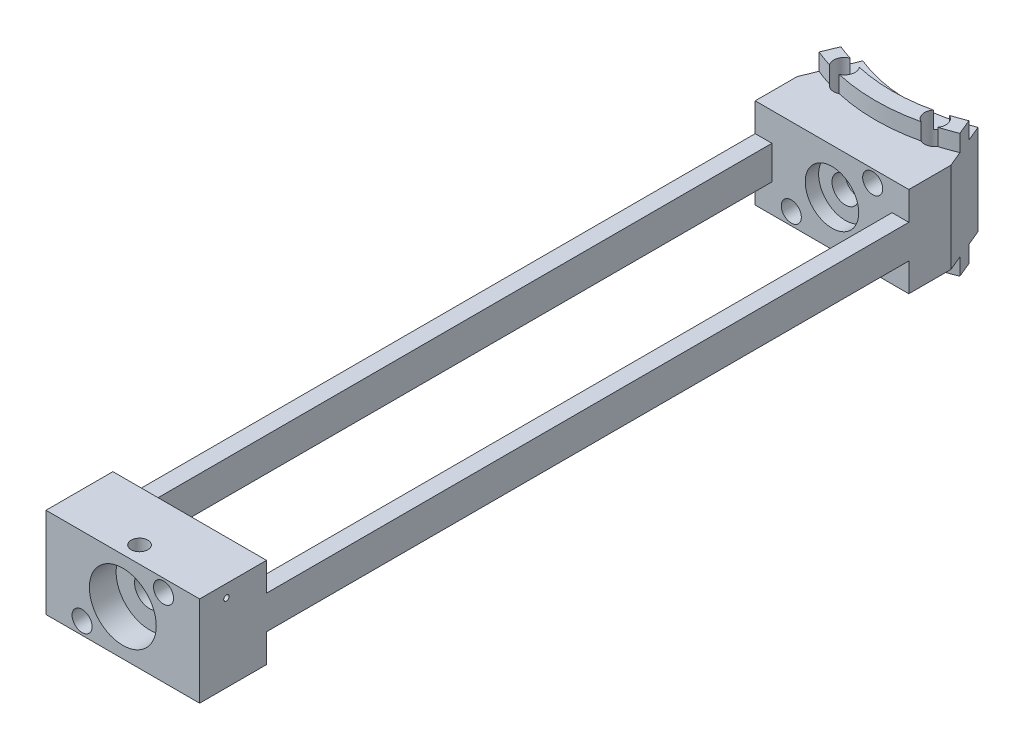
SolidWorks part; units mm, degrees
note: The reader was unsure of these and kept them because the rebuilt part matched: shared geometry of "Sketch1<3>".
ref_plane "Front Plane" through (0, 0, 0) normal (0, 0, 1) x (1, 0, 0)
ref_plane "Top Plane" through (0, 0, 0) normal (0, 1, 0) x (1, 0, 0)
ref_plane "Right Plane" through (0, 0, 0) normal (1, 0, 0) x (0, 0, -1)
sketch "Sketch1" plane through (0, 0, 0) normal (0, 1, 0) x (1, 0, 0)
  line L0 (0, 0) -> (-22.961, -55.4328)
  line L1 (0, 0) -> (22.961, -55.4328)
  line L2 (0, 0) -> (0, -29.5283) construction
  circle A0 centre (0, 0) radius 60
  circle A1 centre (0, 0) radius 55
  circle A2 centre (0, 0) radius 50
  circle A3 centre (0, 0) radius 45
  dimension "D1" = 120
  dimension "D2" = 5
  dimension "D3" = 5
  dimension "D4" = 5
  dimension "D5" = 45
extrude "Boss-Extrude1" add sketch "Sketch1" along normal mid plane 27 contours A1 L0 A0 L1 | A2 L0 A1 L1 | A3 L0 A2 L1
extrude "Boss-Extrude2" add sketch "Sketch1<3>" along normal mid plane 37 contours A2 L0 A1 L1
sketch "Sketch1<3>" plane through (0, 0, 0) normal (0, 1, 0) x (1, 0, 0) same geometry as "Sketch1"
ref_plane "Plane1" through (0, 0, 60) normal (0, 0, 1) x (1, 0, 0)
sketch "Sketch3" plane through (0, 0, 0) normal (0, -1, 0) x (1, 0, 0)
  line L0 (-22.961, 55.4328) -> (-22.961, 280)
  line L1 (-22.961, 280) -> (22.961, 280)
  line L2 (22.961, 280) -> (22.961, 55.4328)
  line L3 (-17.961, 57.2486) -> (-17.961, 260)
  line L4 (-17.961, 260) -> (17.961, 260)
  line L5 (17.961, 260) -> (17.961, 57.2486)
  arc A0 (22.961, 55.4328) -> (-22.961, 55.4328) centre (0, 0) ccw construction
  arc A1 (22.961, 55.4328) -> (-22.961, 55.4328) centre (0, 0) ccw
  dimension "D1" = 5
  dimension "D2" = 5
  dimension "D3" = 20
  dimension "D4" = 280
extrude "Boss-Extrude3" add sketch "Sketch3" against normal mid plane 10 contours L3 A1 L0 L1 L2 L5 L4
sketch "Sketch4" plane through (0, 0, 0) normal (0, 1, 0) x (1, 0, 0)
  line L0 (22.961, -280) -> (22.961, -55.4328) construction
  line L1 (-22.961, -280) -> (22.961, -280)
  line L2 (-22.961, -280) -> (-22.961, -260)
  line L3 (-22.961, -260) -> (22.961, -260)
  line L4 (22.961, -280) -> (22.961, -260)
  line L5 (-17.961, -260) -> (17.961, -260) construction
extrude "Boss-Extrude4" add sketch "Sketch4" along normal mid plane 27
sketch "Sketch2" plane through (0, 0, 0) normal (0, 0, 1) x (1, 0, 0)
  circle A0 centre (0, 0) radius 4
  dimension "D1" = 8
extrude "Cut-Extrude1" cut sketch "Sketch2" along normal through all
sketch "Sketch5" plane through (0, 0, 260) normal (0, 0, -1) x (-1, 0, 0)
  circle A0 centre (0, 0) radius 8
  dimension "D1" = 16
extrude "Cut-Extrude2" cut sketch "Sketch5" against normal blind 4 contours A0
sketch "Sketch6" plane through (0, 0, 280) normal (0, 0, 1) x (1, 0, 0)
  circle A0 centre (0, 0) radius 10
  dimension "D1" = 20
extrude "Cut-Extrude3" cut sketch "Sketch6" against normal blind 8
sketch "Sketch7" plane through (0, 0, 280) normal (0, 0, 1) x (1, 0, 0)
  circle A0 centre (0, 0) radius 10
  dimension "D1" = 20
sketch "Sketch9" plane through (0, 0, 0) normal (0, 1, 0) x (1, 0, 0)
  line L0 (-22.961, -55.4328) -> (-22.961, -68)
  line L1 (-22.961, -55.4328) -> (-22.961, -260) construction
  line L2 (-22.961, -68) -> (22.961, -68)
  line L3 (22.961, -260) -> (22.961, -55.4328) construction
  line L4 (22.961, -68) -> (22.961, -55.4328)
  arc A0 (-22.961, -55.4328) -> (22.961, -55.4328) centre (0, 0) ccw construction
  arc A1 (-22.961, -55.4328) -> (22.961, -55.4328) centre (0, 0) ccw
  point P3 (0, -60)
  dimension "D1" = 8
extrude "Boss-Extrude5" add sketch "Sketch9" along normal mid plane 27
sketch "Sketch8" plane through (0, 0, 60) normal (0, 0, 1) x (1, 0, 0)
  circle A0 centre (0, 0) radius 9
  dimension "D1" = 18
extrude "Cut-Extrude5" cut sketch "Sketch8" against normal up to next
sketch "Sketch10" plane through (0, 0, 60) normal (0, 0, 1) x (1, 0, 0)
  circle A0 centre (0, 0) radius 4
  dimension "D1" = 8
extrude "Cut-Extrude6" cut sketch "Sketch10" along normal up to next
sketch "Sketch11" plane through (0, 0, 68) normal (0, 0, 1) x (1, 0, 0)
  circle A0 centre (0, 0) radius 8
  dimension "D1" = 16
extrude "Cut-Extrude7" cut sketch "Sketch11" against normal blind 4
sketch "Sketch15" plane through (0, 0, 280) normal (0, 0, 1) x (1, 0, 0)
  circle A0 centre (-12.1674, -9.7628) radius 3
  circle A1 centre (12.1674, 9.7628) radius 3
  dimension "D1" = 6
extrude "Cut-Extrude8" cut sketch "Sketch15" against normal up to vertex (224.5672 mm away) contours A0 | A1
hole_wizard "M2 Tapped Hole1" positions "Sketch16" profile "Sketch17" tap size "M2" standard "ISO"
sketch "Sketch16" plane through (22.961, 0, 0) normal (1, 0, 0) x (0, 0, -1)
  line L2 (-280, 13.5) -> (-260, 13.5) construction
  line L3 (-280, 13.5) -> (-280, -13.5) construction
  point P0 (-272, 9.7628)
  dimension "D1" = 3.7372
  dimension "D2" = 8
sketch "Sketch17" plane through (22.961, 9.7628, 272) normal (0, 1, 0) x (0, 0, -1)
  line L0 (0, 0) -> (0, 10.4807)
  line L1 (0, 10.4807) -> (0.8, 10)
  line L2 (0.8, 10) -> (0.8, 0)
  line L5 (0.8, 0) -> (0, 0)
  line L10 (0, 10.4807) -> (-0.8, 10) construction
  line L11 (0, -6.35) -> (0, 107.95) construction
  dimension "Tap Drill Dia." = 1.6
  dimension "Tap Drill Depth" = 10
  dimension "Drill Angle" = 118
cosmetic thread "Hole Thread1" parameters "D1"=4, "D2"=2
hole_wizard "M6 Clearance Hole1" positions "Sketch18" profile "Sketch19" hole size "M6" standard "ISO" end condition through all
sketch "Sketch18" plane through (0, 18.5, 0) normal (0, 1, 0) x (1, 0, 0)
  line L0 (0, 0) -> (-13.588, -50.7111) construction
  line L1 (0, 0) -> (13.588, -50.7111) construction
  line L2 (0, 0) -> (0, -37.9103) construction
  line L3 (-14.235, -53.1259) -> (-12.941, -48.2963) construction
  line L4 (-14.235, -53.1259) -> (-26.4736, -49.8466) construction
  arc A0 (-21.0476, -50.8134) -> (21.0476, -50.8134) centre (0, 0) ccw construction
  arc A1 (-19.1342, -46.194) -> (19.1342, -46.194) centre (0, 0) ccw construction
  arc A3 (-21.0476, -50.8134) -> (21.0476, -50.8134) centre (0, 0) ccw construction
  point P0 (13.588, -50.7111)
  point P2 (-13.588, -50.7111)
  dimension "D1" = 30
sketch "Sketch19" plane through (13.588, 18.5, 50.7111) normal (1, 0, 0) x (0, 0, 1)
  line L0 (0, 0) -> (0, 37)
  line L1 (0, 37) -> (3.2, 37)
  line L2 (3.2, 37) -> (3.2, 0)
  line L5 (3.2, 0) -> (0, 0)
  line L11 (0, -6.35) -> (0, 107.95) construction
  dimension "Thru Hole Dia." = 6.4
  dimension "Thru Hole Depth" = 37
sketch "Sketch20" plane through (0, 0, 272) normal (0, 0, 1) x (1, 0, 0)
  circle A0 centre (0, 0) radius 4.5
  dimension "D1" = 9
extrude "Cut-Extrude9" cut sketch "Sketch20" against normal up to next
pattern_circular "CirPattern1" count 2 over 360 about axis through (0, 0, 272) along (1, 0, 0) of "M2 Tapped Hole1"
sketch "Sketch21" plane through (0, 13.5, 0) normal (0, 1, 0) x (1, 0, 0)
  line L0 (-22.961, -280) -> (22.961, -280) construction
  circle A0 centre (0, -275) radius 2.5
  dimension "D2" = 5
  dimension "D1" = 5
extrude "Cut-Extrude10" cut sketch "Sketch21" against normal up to next
sketch "Sketch22" plane through (0, 0, 0) normal (0, 0, 1) x (1, 0, 0)
  circle A0 centre (0, 0) radius 11
  dimension "D1" = 22
extrude "Cut-Extrude11" cut sketch "Sketch22" along normal blind 47
